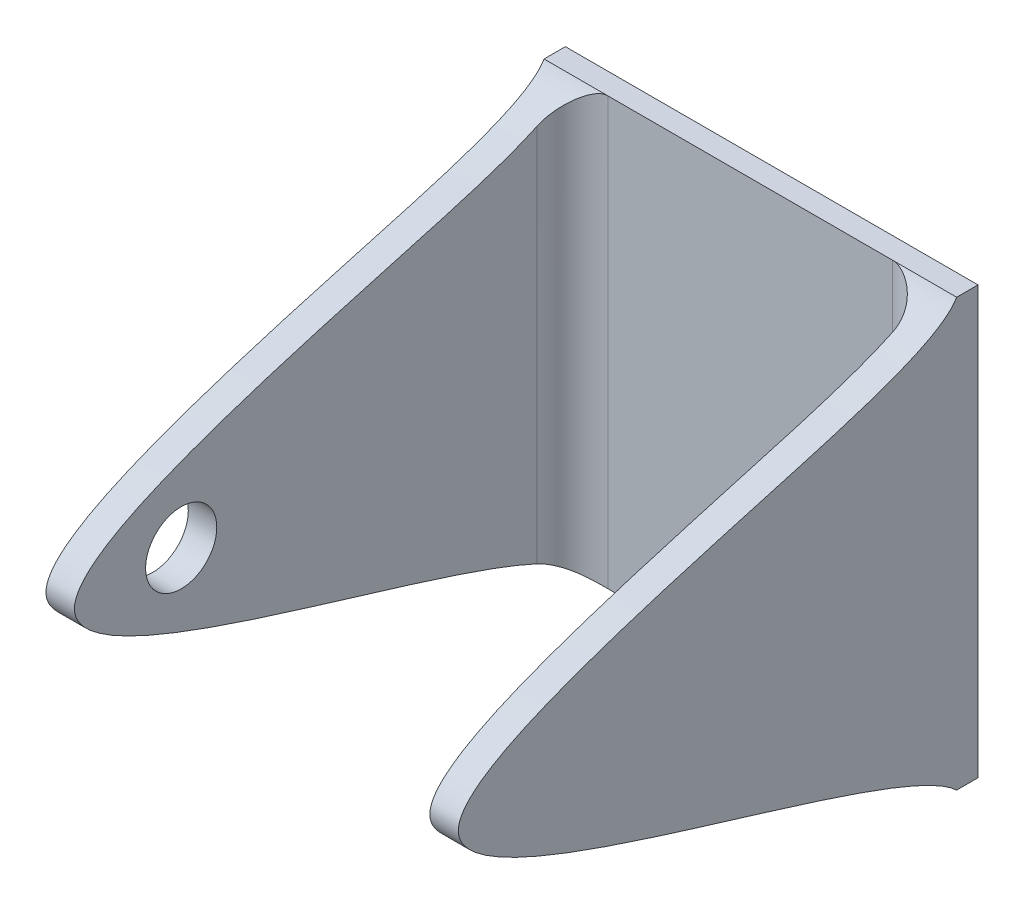
SolidWorks part; units mm, degrees
ref_plane "Front Plane" through (0, 0, 0) normal (1, 0, 0) x (0, 1, 0)
ref_plane "Top Plane" through (0, 0, 0) normal (0, 0, 1) x (0, 1, 0)
ref_plane "Right Plane" through (0, 0, 0) normal (0, 1, 0) x (-1, 0, 0)
sketch "Sketch2" plane through (0, 0, 0) normal (1, 0, 0) x (0, 1, 0)
  line L0 (-30, -28) -> (30, -28)
  line L1 (79.8099, 0) -> (-79.8099, 0) construction
  circle A0 centre (0, 27) radius 5
  spline S0 degree 3 poles (-30, -28) (-21.3579, -18.8979) (-4.5887, 78.4276) (17.7927, 5.8908) (25.8559, -25.6434) (30, -28) knots 0 0 0 0 0.42802 0.687018 0.856039 0.856039 0.856039 0.856039
  point P2 (0, -28)
  point P3 (-19, 0)
  point P4 (0, 42)
  point P8 (0, 0)
  point P9 (19, 0)
  dimension "D3" = 70
  dimension "D4" = 19
  dimension "D6" = 14.3018
  dimension "D7" = 155.2946
  dimension "D8" = 10
  dimension "D1" = 60
  dimension "D2" = 28
  dimension "D5" = 19
  dimension "D9" = 15
ref_plane "Plane1" through (50, 0, 0) normal (1, 0, 0) x (0, 1, 0)
sketch "Sketch6" plane through (50, 0, 0) normal (1, 0, 0) x (0, 1, 0)
  line L0 (-30, -28) -> (30, -28)
  line L1 (79.8099, 0) -> (-79.8099, 0) construction
  circle A0 centre (0, 27.0425) radius 5
  spline S0 degree 3 poles (-30, -28) (-21.3412, -18.9336) (-4.314, 78.5223) (17.3034, 5.8775) (25.8559, -25.6434) (30, -28) knots 0 0 0 0 0.42802 0.687018 0.856039 0.856039 0.856039 0.856039
  point P2 (0, -28)
  point P3 (-18.9425, 0)
  point P4 (0, 42.0425)
  point P7 (0, 0)
  point P8 (18.7494, 0)
  point P14 (0, 0)
  point P16 (0, 0)
  dimension "D2" = 14.3018
  dimension "D3" = 155.2911
  dimension "D6" = 10
  dimension "D1" = 15
  dimension "D4" = 28
  dimension "D5" = 60
extrude "Boss-Extrude1" add sketch "Sketch6" along normal blind 4 contours S0 L0
extrude "Boss-Extrude2" add sketch "Sketch2" against normal blind 4 separate body contours S0 L0
sketch "Sketch7" plane through (0, 0, -28) normal (0, 0, -1) x (0, 1, 0)
  line L1 (-30, -4) -> (30, -4)
  line L2 (-30, -4) -> (-30, 54)
  line L3 (-30, 54) -> (30, 54)
  line L4 (30, -4) -> (30, 54)
extrude "Boss-Extrude3" add sketch "Sketch7" along normal blind 3
fillet "Fillet2" radius 5 2 edges at (50, 0, -28) (0, 0, -28)
extrude "Cut-Extrude1" cut sketch "Sketch2<4>" against normal blind 5 contours A0
sketch "Sketch2<4>" plane through (0, 0, 0) normal (1, 0, 0) x (0, 1, 0) same geometry as "Sketch2"
